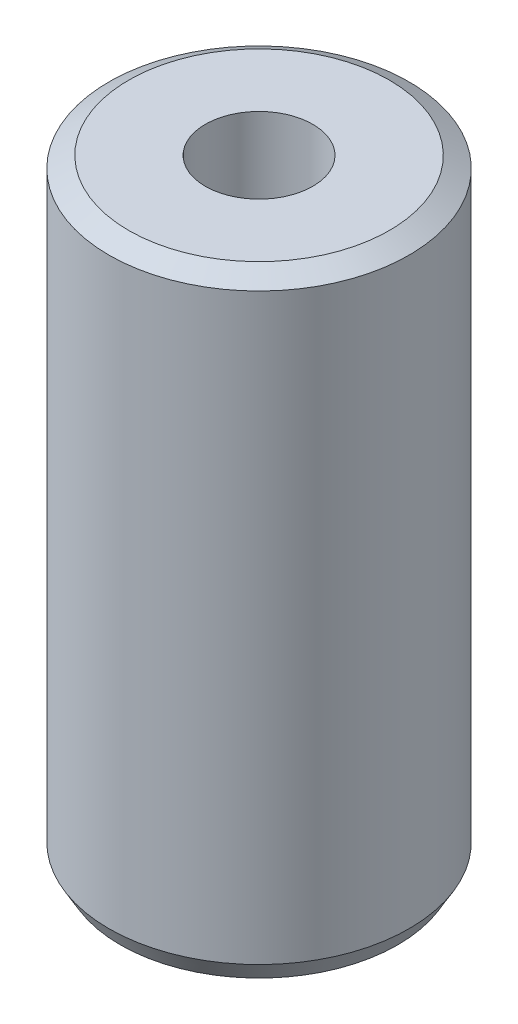
SolidWorks part; units mm, degrees
ref_plane "Front Plane" through (0, 0, 0) normal (0, 0, 1) x (1, 0, 0)
ref_plane "Top Plane" through (0, 0, 0) normal (0, 1, 0) x (1, 0, 0)
ref_plane "Right Plane" through (0, 0, 0) normal (1, 0, 0) x (0, 0, -1)
sketch "Sketch1" plane through (0, 0, 0) normal (0, 1, 0) x (1, 0, 0)
  circle A0 centre (0, 0) radius 57.5
  dimension "SHAFT_OD" = 115
extrude "Boss-Extrude1" add sketch "Sketch1" along normal blind 235.427
sketch "Sketch2" plane through (0, 0, 0) normal (0, 1, 0) x (1, 0, 0)
  circle A0 centre (0, 0) radius 20.5896
  dimension "BORE_D" = 41.1792
extrude "Cut-Extrude1" cut sketch "Sketch2" along normal through all
chamfer "Chamfer1" distance 4.3777 angle 60 2 edges at (0, 235.427, 57.5) (0, 0, 57.5) first distance on face at (0, 235.427, 57.5) first distance on face at (0, 0, 20.5896)
